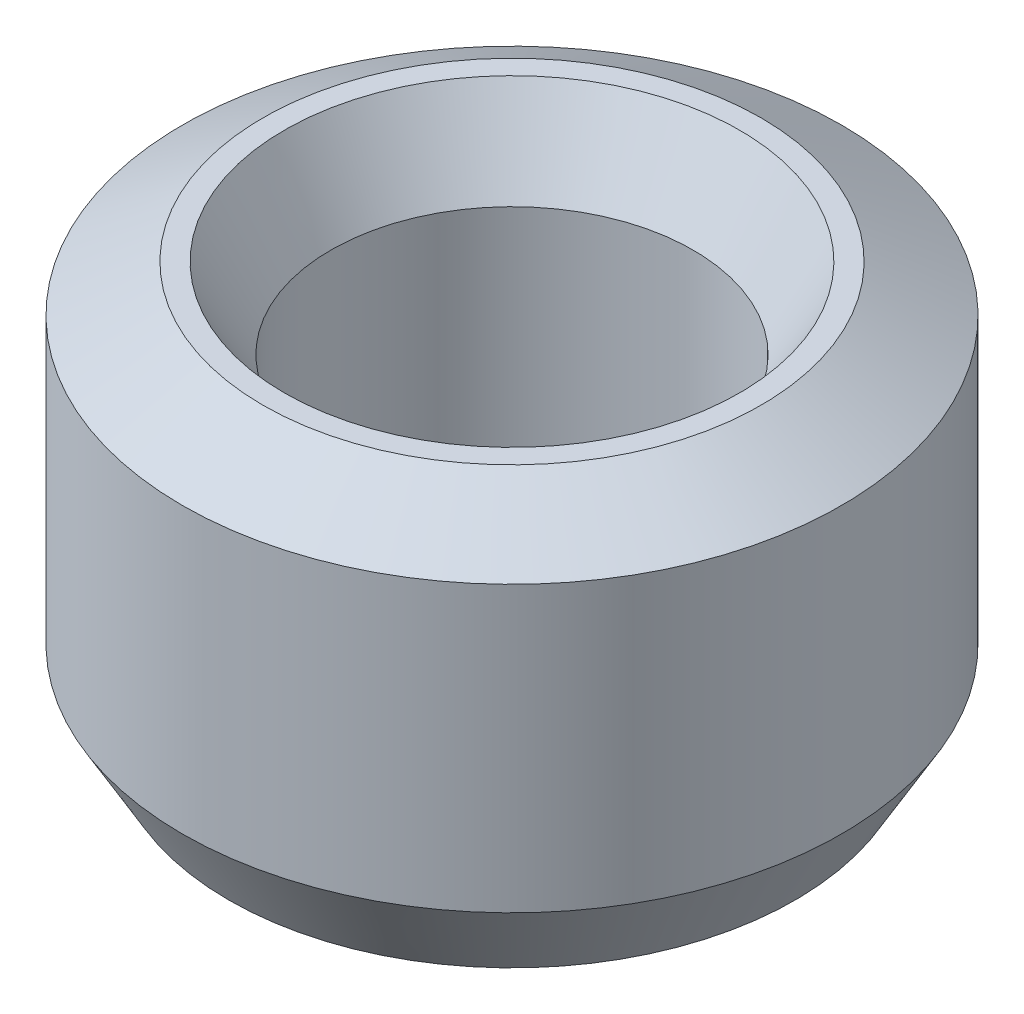
SolidWorks part; units mm, degrees
ref_plane "Front Plane" through (0, 0, 0) normal (0, 0, 1) x (1, 0, 0)
ref_plane "Top Plane" through (0, 0, 0) normal (0, 1, 0) x (1, 0, 0)
ref_plane "Right Plane" through (0, 0, 0) normal (1, 0, 0) x (0, 0, -1)
sketch "Sketch1" plane through (0, 0, 0) normal (0, 1, 0) x (1, 0, 0)
  circle A0 centre (0, 0) radius 5
  dimension "SLEEVE_OD" = 10
extrude "Boss-Extrude1" add sketch "Sketch1" along normal blind 6.2445
sketch "Sketch2" plane through (0, 0, 0) normal (0, 1, 0) x (1, 0, 0)
  circle A0 centre (0, 0) radius 2.7479
  dimension "BORE_D" = 5.4957
extrude "Cut-Extrude1" cut sketch "Sketch2" along normal through all
chamfer "Chamfer1" distance 0.7057 angle 60 4 edges at (0, 6.2445, 2.7479) (0, 0, 2.7479) (0, 0, 5) (0, 6.2445, 5) first distance on face at (0, 6.2445, 2.7479) first distance on face at (0, 0, 2.7479) first distance on face at (0, 6.2445, 5)
